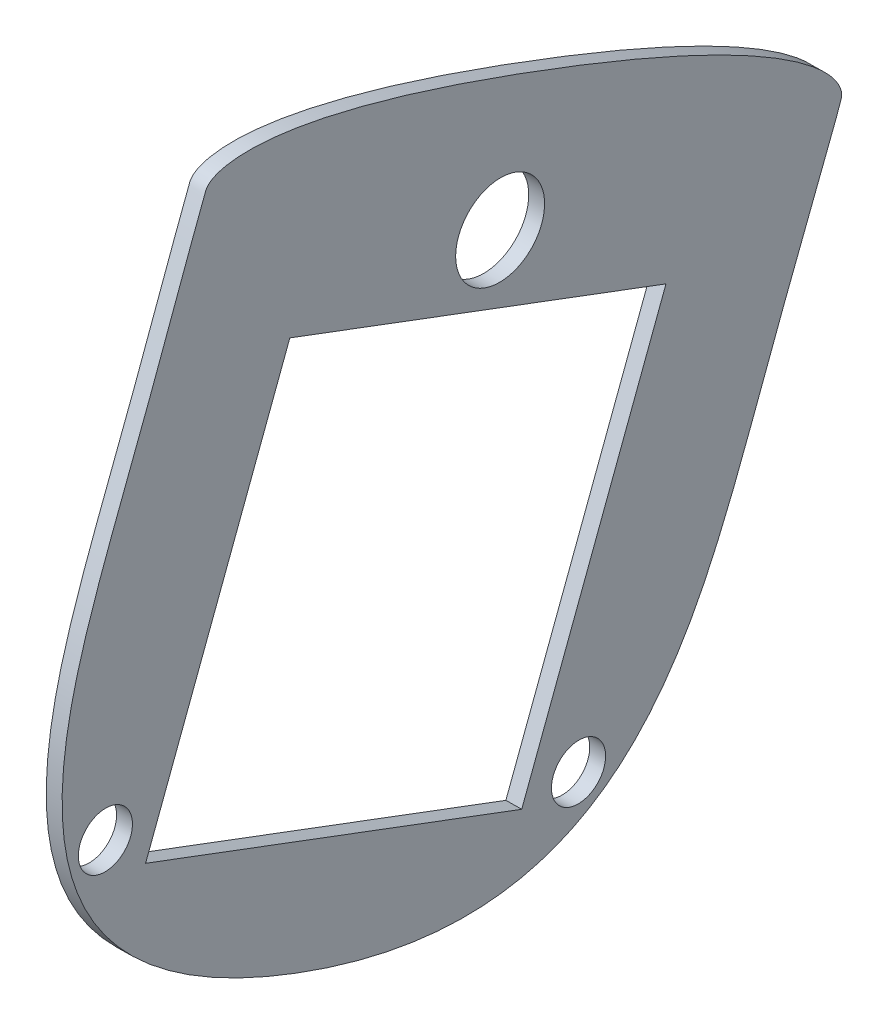
SolidWorks part; units mm, degrees
ref_plane "Front Plane" through (0, 0, 0) normal (0, 0, 1) x (1, 0, 0)
ref_plane "Top Plane" through (0, 0, 0) normal (0, 1, 0) x (1, 0, 0)
ref_plane "Right Plane" through (0, 0, 0) normal (1, 0, 0) x (0, 0, -1)
sketch "Sketch2" plane through (-865.3739, -0.0001, 10.9842) normal (-0.9999, 0, 0.0127) x (0.0127, 0, 0.9999)
  circle A0 centre (-17.1866, -9.2159) radius 6 construction
  circle A1 centre (105.1276, 37.6907) radius 6 construction
  circle A2 centre (-17.1866, -9.2159) radius 6
  circle A3 centre (105.1276, 37.6907) radius 6
  circle A4 centre (2.5155, 122.3361) radius 11.5 construction
  circle A5 centre (2.5155, 122.3361) radius 11.5
  point P0 (84.5639, 170.2439)
  point P1 (79.9592, 168.2953)
  dimension "D4" = 23
  dimension "D1" = 5
ref_plane "Plane1" through (-1179.5486, -0.0001, 14.972) normal (-0.9999, 0, 0.0127) x (0.0127, 0, 0.9999)
sketch "Sketch3" plane through (-1179.5486, -0.0001, 14.972) normal (-0.9999, 0, 0.0127) x (0.0127, 0, 0.9999)
  line L2 (-2.4987, -10.0092) -> (94.7364, 27.2797)
  line L6 (94.7364, 27.2797) -> (57.4475, 124.5149)
  line L7 (57.4475, 124.5149) -> (-39.7876, 87.2259)
  line L8 (-39.7876, 87.2259) -> (-2.4987, -10.0092)
  circle A3 centre (105.1276, 37.6907) radius 7
  circle A8 centre (3.0884, 120.8422) radius 11.5
  circle A9 centre (-17.1866, -9.2159) radius 7
  spline S0 degree 3 poles (84.5877, 169.5548) (84.1591, 170.6141) (83.6114, 171.6458) (82.4825, 172.9682) (81.1275, 174.0328) (79.6255, 174.8519) (78.0481, 175.4677) (75.8837, 176.0674) (73.1375, 176.4938) (69.8483, 176.6685) (66.5932, 176.6095) (63.379, 176.3823) (60.2073, 176.0282) (57.0754, 175.5759) (53.9806, 175.0444) (50.9193, 174.4483) (47.8886, 173.7975) (44.8855, 173.1008) (40.9147, 172.1178) (36.0066, 170.8019) (30.1862, 169.1128) (24.4167, 167.3312) (18.6809, 165.471) (12.9629, 163.5374) (7.2468, 161.5366) (-0.3928, 158.7797) (-6.166, 156.6131) (-13.9483, 153.6286) (-19.6897, 151.3795) (-27.2134, 148.3214) (-32.8014, 145.9872) (-38.3459, 143.6017) (-43.8547, 141.1498) (-49.3359, 138.6168) (-54.7932, 135.9811) (-59.3225, 133.6777) (-62.9324, 131.7536) (-65.6313, 130.2638) (-68.3201, 128.7213) (-70.995, 127.1176) (-73.6517, 125.4434) (-76.283, 123.6856) (-78.8782, 121.8282) (-81.4203, 119.8479) (-83.8804, 117.7153) (-86.2094, 115.386) (-87.9665, 113.2326) (-89.1751, 111.3395) (-89.9363, 109.8267) (-90.5056, 108.2133) (-90.8014, 106.5155) (-90.7567, 104.7772) (-90.474, 103.6437) (-90.0844, 102.5695) (-89.841, 101.912) (-89.5415, 101.1241) (-89.3902, 100.7305) (-89.238, 100.337) (-89.086, 99.9434) (-88.9335, 99.5497) (-88.7301, 99.0246) (-88.3735, 98.1053) (-87.8622, 96.7909) (-87.2459, 95.2119) (-86.6271, 93.6311) (-86.006, 92.0484) (-85.3828, 90.4637) (-84.7576, 88.8772) (-84.1306, 87.2885) (-83.5021, 85.6979) (-82.662, 83.5742) (-81.6087, 80.9142) (-80.341, 77.7134) (-79.0707, 74.5033) (-77.7994, 71.2836) (-76.5287, 68.0539) (-75.2594, 64.814) (-73.9927, 61.5637) (-72.7309, 58.3024) (-71.4763, 55.0294) (-69.81, 50.6514) (-67.733, 45.1559) (-65.1929, 38.5485) (-63.0021, 33.047) (-61.1797, 28.6615) (-60.0063, 25.9297) (-59.0438, 23.7513) (-58.3093, 22.1218) (-57.5611, 20.497) (-56.7986, 18.8776) (-56.0207, 17.2642) (-55.227, 15.6574) (-54.4159, 14.0579) (-52.7551, 10.8759) (-50.1136, 6.1705) (-46.2141, 0.1062) (-41.8798, -5.6826) (-37.071, -11.0955) (-31.7493, -16.031) (-26.8927, -19.6435) (-22.7717, -22.1827) (-18.509, -24.4734) (-12.9357, -26.8488) (-5.9687, -28.8976) (1.1735, -30.1678) (8.3946, -30.7243) (15.6292, -30.6392) (22.8222, -29.9927) (29.9449, -28.8562) (36.9714, -27.3105) (46.201, -24.7823) (52.9582, -22.4509) (61.8197, -19.0525) (68.4041, -16.2675) (76.9584, -11.9755) (83.2171, -8.426) (89.2737, -4.508) (95.0546, -0.1787) (100.4909, 4.596) (105.488, 9.8386) (109.9491, 15.5591) (113.7592, 21.7413) (116.3146, 27.2342) (117.9522, 31.7877) (119.3182, 36.4313) (120.5136, 42.3647) (121.1702, 49.5927) (121.1263, 56.8326) (120.4783, 64.0347) (119.3229, 71.151) (118.1408, 76.4157) (117.2481, 79.8921) (116.7817, 81.6236) (116.2975, 83.349) (115.7971, 85.0687) (115.2813, 86.7826) (114.7512, 88.4909) (114.2078, 90.1937) (113.467, 92.4568) (112.5129, 95.2725) (110.9356, 99.7518) (108.8862, 105.3072) (106.3571, 111.9184) (104.227, 117.3933) (102.5388, 121.7627) (101.2832, 125.0351) (100.0408, 128.3038) (98.8095, 131.5676) (97.5869, 134.8253) (96.3723, 138.0765) (95.1647, 141.3206) (93.9629, 144.5568) (92.7653, 147.7846) (91.7699, 150.4668) (90.9746, 152.6077) (90.3784, 154.2108) (89.7824, 155.8113) (89.1863, 157.4091) (88.5902, 159.0041) (87.9938, 160.5963) (87.3968, 162.1856) (86.7993, 163.7719) (86.3006, 165.0911) (85.9511, 166.0132) (85.7512, 166.5397) (85.6013, 166.9344) (85.4511, 167.3288) (85.3012, 167.7231) (85.1505, 168.117) (84.8464, 168.9032) (84.5877, 169.5548) (84.1591, 170.6141) (83.6114, 171.6458) knots -0.00321 -0.002568 0 0 0.002678 0.005356 0.008033 0.010711 0.013389 0.016067 0.021422 0.026778 0.032133 0.037489 0.042844 0.0482 0.053555 0.058911 0.064266 0.069622 0.074977 0.085688 0.096399 0.10711 0.117821 0.128532 0.139243 0.149955 0.171377 0.171377 0.192798 0.203509 0.21422 0.224931 0.235641 0.246352 0.257063 0.267774 0.273129 0.278485 0.28384 0.289196 0.294551 0.299906 0.305262 0.310617 0.315973 0.321328 0.326683 0.329361 0.332039 0.334717 0.337394 0.340072 0.34275 0.34275 0.345317 0.345958 0.3466 0.347242 0.347884 0.348525 0.349167 0.350451 0.353018 0.355585 0.358152 0.360719 0.363286 0.365853 0.36842 0.370987 0.373554 0.378688 0.383822 0.388956 0.39409 0.399224 0.404358 0.409492 0.414626 0.419761 0.424895 0.435163 0.445431 0.455699 0.460833 0.465967 0.468534 0.471101 0.473668 0.476235 0.478802 0.481369 0.483936 0.486503 0.496771 0.507039 0.517308 0.527576 0.537844 0.548112 0.553246 0.55838 0.568648 0.578916 0.589184 0.599453 0.609721 0.619989 0.630257 0.640525 0.650793 0.671329 0.671329 0.691871 0.702142 0.712413 0.722684 0.732955 0.743226 0.753497 0.763768 0.774039 0.78431 0.789445 0.794581 0.804852 0.815123 0.825394 0.835665 0.845936 0.856207 0.858774 0.861342 0.86391 0.866478 0.869045 0.871613 0.874181 0.876748 0.881884 0.887019 0.89729 0.907561 0.917832 0.922968 0.928103 0.933239 0.938374 0.94351 0.948645 0.953781 0.958916 0.964052 0.969187 0.971755 0.974323 0.97689 0.979458 0.982026 0.984594 0.987161 0.989729 0.992297 0.993581 0.994223 0.994865 0.995506 0.996148 0.99679 0.997432 1 1 1.002678 1.005356 1.008033 only from (84.3779, 170.0733) to (84.3779, 170.0733)
  spline S1 degree 3 poles (84.5877, 169.5548) (84.1591, 170.6141) (83.6114, 171.6458) (82.4825, 172.9682) (81.1275, 174.0328) (79.6255, 174.8519) (78.0481, 175.4677) (75.8837, 176.0674) (73.1375, 176.4938) (69.8483, 176.6685) (66.5932, 176.6095) (63.379, 176.3823) (60.2073, 176.0282) (57.0754, 175.5759) (53.9806, 175.0444) (50.9193, 174.4483) (47.8886, 173.7975) (44.8855, 173.1008) (40.9147, 172.1178) (36.0066, 170.8019) (30.1862, 169.1128) (24.4167, 167.3312) (18.6809, 165.471) (12.9629, 163.5374) (7.2468, 161.5366) (-0.3928, 158.7797) (-6.166, 156.6131) (-13.9483, 153.6286) (-19.6897, 151.3795) (-27.2134, 148.3214) (-32.8014, 145.9872) (-38.3459, 143.6017) (-43.8547, 141.1498) (-49.3359, 138.6168) (-54.7932, 135.9811) (-59.3225, 133.6777) (-62.9324, 131.7536) (-65.6313, 130.2638) (-68.3201, 128.7213) (-70.995, 127.1176) (-73.6517, 125.4434) (-76.283, 123.6856) (-78.8782, 121.8282) (-81.4203, 119.8479) (-83.8804, 117.7153) (-86.2094, 115.386) (-87.9665, 113.2326) (-89.1751, 111.3395) (-89.9363, 109.8267) (-90.5056, 108.2133) (-90.8014, 106.5155) (-90.7567, 104.7772) (-90.474, 103.6437) (-90.0844, 102.5695) (-89.841, 101.912) (-89.5415, 101.1241) (-89.3902, 100.7305) (-89.238, 100.337) (-89.086, 99.9434) (-88.9335, 99.5497) (-88.7301, 99.0246) (-88.3735, 98.1053) (-87.8622, 96.7909) (-87.2459, 95.2119) (-86.6271, 93.6311) (-86.006, 92.0484) (-85.3828, 90.4637) (-84.7576, 88.8772) (-84.1306, 87.2885) (-83.5021, 85.6979) (-82.662, 83.5742) (-81.6087, 80.9142) (-80.341, 77.7134) (-79.0707, 74.5033) (-77.7994, 71.2836) (-76.5287, 68.0539) (-75.2594, 64.814) (-73.9927, 61.5637) (-72.7309, 58.3024) (-71.4763, 55.0294) (-69.81, 50.6514) (-67.733, 45.1559) (-65.1929, 38.5485) (-63.0021, 33.047) (-61.1797, 28.6615) (-60.0063, 25.9297) (-59.0438, 23.7513) (-58.3093, 22.1218) (-57.5611, 20.497) (-56.7986, 18.8776) (-56.0207, 17.2642) (-55.227, 15.6574) (-54.4159, 14.0579) (-52.7551, 10.8759) (-50.1136, 6.1705) (-46.2141, 0.1062) (-41.8798, -5.6826) (-37.071, -11.0955) (-31.7493, -16.031) (-26.8927, -19.6435) (-22.7717, -22.1827) (-18.509, -24.4734) (-12.9357, -26.8488) (-5.9687, -28.8976) (1.1735, -30.1678) (8.3946, -30.7243) (15.6292, -30.6392) (22.8222, -29.9927) (29.9449, -28.8562) (36.9714, -27.3105) (46.201, -24.7823) (52.9582, -22.4509) (61.8197, -19.0525) (68.4041, -16.2675) (76.9584, -11.9755) (83.2171, -8.426) (89.2737, -4.508) (95.0546, -0.1787) (100.4909, 4.596) (105.488, 9.8386) (109.9491, 15.5591) (113.7592, 21.7413) (116.3146, 27.2342) (117.9522, 31.7877) (119.3182, 36.4313) (120.5136, 42.3647) (121.1702, 49.5927) (121.1263, 56.8326) (120.4783, 64.0347) (119.3229, 71.151) (118.1408, 76.4157) (117.2481, 79.8921) (116.7817, 81.6236) (116.2975, 83.349) (115.7971, 85.0687) (115.2813, 86.7826) (114.7512, 88.4909) (114.2078, 90.1937) (113.467, 92.4568) (112.5129, 95.2725) (110.9356, 99.7518) (108.8862, 105.3072) (106.3571, 111.9184) (104.227, 117.3933) (102.5388, 121.7627) (101.2832, 125.0351) (100.0408, 128.3038) (98.8095, 131.5676) (97.5869, 134.8253) (96.3723, 138.0765) (95.1647, 141.3206) (93.9629, 144.5568) (92.7653, 147.7846) (91.7699, 150.4668) (90.9746, 152.6077) (90.3784, 154.2108) (89.7824, 155.8113) (89.1863, 157.4091) (88.5902, 159.0041) (87.9938, 160.5963) (87.3968, 162.1856) (86.7993, 163.7719) (86.3006, 165.0911) (85.9511, 166.0132) (85.7512, 166.5397) (85.6013, 166.9344) (85.4511, 167.3288) (85.3012, 167.7231) (85.1505, 168.117) (84.8464, 168.9032) (84.5877, 169.5548) (84.1591, 170.6141) (83.6114, 171.6458) knots -0.00321 -0.002568 0 0 0.002678 0.005356 0.008033 0.010711 0.013389 0.016067 0.021422 0.026778 0.032133 0.037489 0.042844 0.0482 0.053555 0.058911 0.064266 0.069622 0.074977 0.085688 0.096399 0.10711 0.117821 0.128532 0.139243 0.149955 0.171377 0.171377 0.192798 0.203509 0.21422 0.224931 0.235641 0.246352 0.257063 0.267774 0.273129 0.278485 0.28384 0.289196 0.294551 0.299906 0.305262 0.310617 0.315973 0.321328 0.326683 0.329361 0.332039 0.334717 0.337394 0.340072 0.34275 0.34275 0.345317 0.345958 0.3466 0.347242 0.347884 0.348525 0.349167 0.350451 0.353018 0.355585 0.358152 0.360719 0.363286 0.365853 0.36842 0.370987 0.373554 0.378688 0.383822 0.388956 0.39409 0.399224 0.404358 0.409492 0.414626 0.419761 0.424895 0.435163 0.445431 0.455699 0.460833 0.465967 0.468534 0.471101 0.473668 0.476235 0.478802 0.481369 0.483936 0.486503 0.496771 0.507039 0.517308 0.527576 0.537844 0.548112 0.553246 0.55838 0.568648 0.578916 0.589184 0.599453 0.609721 0.619989 0.630257 0.640525 0.650793 0.671329 0.671329 0.691871 0.702142 0.712413 0.722684 0.732955 0.743226 0.753497 0.763768 0.774039 0.78431 0.789445 0.794581 0.804852 0.815123 0.825394 0.835665 0.845936 0.856207 0.858774 0.861342 0.86391 0.866478 0.869045 0.871613 0.874181 0.876748 0.881884 0.887019 0.89729 0.907561 0.917832 0.922968 0.928103 0.933239 0.938374 0.94351 0.948645 0.953781 0.958916 0.964052 0.969187 0.971755 0.974323 0.97689 0.979458 0.982026 0.984594 0.987161 0.989729 0.992297 0.993581 0.994223 0.994865 0.995506 0.996148 0.99679 0.997432 1 1 1.002678 1.005356 1.008033 only from (84.3779, 170.0733) to (84.3779, 170.0733)
  spline S2 degree 3 poles (79.7703, 168.0973) (79.654, 168.385) (79.5608, 168.567) (79.34, 168.909) (79.2107, 169.0695) (78.782, 169.5156) (78.4531, 169.7564) (77.7463, 170.1738) (77.3742, 170.347) (76.6181, 170.646) (76.2313, 170.7718) (75.4457, 170.9901) (75.0459, 171.0829) (74.2475, 171.2414) (73.8476, 171.3072) (72.6462, 171.473) (71.8432, 171.5429) (69.4298, 171.6691) (67.8151, 171.6433) (64.5792, 171.4656) (62.9671, 171.312) (59.7615, 170.9206) (58.1658, 170.6823) (54.9849, 170.1436) (53.3996, 169.8431) (48.656, 168.8688) (45.5068, 168.1227) (39.2498, 166.5091) (36.1403, 165.6406) (29.9484, 163.8155) (26.8662, 162.8586) (17.65, 159.8886) (11.5458, 157.7754) (-0.6049, 153.3792) (-6.6499, 151.0973) (-18.6886, 146.4029) (-24.6805, 143.9847) (-36.5791, 138.946) (-42.4872, 136.3273) (-51.2341, 132.1553) (-54.1301, 130.7232) (-59.8634, 127.7454) (-62.7011, 126.2002) (-66.8856, 123.7579) (-68.2675, 122.9231) (-70.9987, 121.2004) (-72.3487, 120.3119) (-74.9994, 118.4656) (-76.2997, 117.5087) (-78.8252, 115.4929) (-80.0492, 114.4377) (-81.7749, 112.7382) (-82.3328, 112.1498) (-83.3836, 110.9299) (-83.8771, 110.2969) (-84.5427, 109.2937) (-84.7517, 108.95) (-85.1321, 108.2356) (-85.3048, 107.8624) (-85.5131, 107.2891) (-85.5741, 107.0954) (-85.6734, 106.7005) (-85.7118, 106.4978) (-85.7567, 106.0923) (-85.7631, 105.8894) (-85.7375, 105.4833) (-85.7033, 105.2783) (-85.5978, 104.885) (-85.5239, 104.6959) (-85.3844, 104.3148) (-85.3142, 104.1244) (-85.1021, 103.5537) (-84.9587, 103.174) (-84.5227, 102.0368) (-84.2284, 101.28) (-83.3473, 99.0091) (-82.7572, 97.4963) (-77.4279, 83.8874) (-72.5683, 71.8388) (-66.7371, 56.6822) (-65.5847, 53.6454) (-63.2813, 47.5713) (-62.1268, 44.5353) (-59.771, 38.4819) (-58.5707, 35.464) (-56.7026, 30.9639) (-56.0686, 29.4684) (-54.7723, 26.4884) (-54.1097, 25.0035) (-50.7192, 17.6341) (-47.7589, 11.8968) (-42.5832, 3.7604) (-40.7366, 1.1258) (-37.7313, -2.6759) (-36.6901, -3.9179) (-35.0604, -5.7377) (-34.5059, -6.337) (-33.3724, -7.5201) (-32.7922, -8.1052) (-29.8441, -10.9713) (-27.345, -13.0666) (-23.3611, -15.8788) (-21.9939, -16.761) (-19.1769, -18.4096) (-17.7261, -19.1766) (-10.2663, -22.7) (-3.9825, -24.3776) (3.3729, -25.2321) (4.1924, -25.3124) (5.8269, -25.4445) (6.6433, -25.4963) (9.09, -25.6118) (10.7178, -25.6352) (15.5924, -25.5618) (18.8302, -25.3221) (23.6723, -24.7256) (25.2838, -24.487) (28.5025, -23.9384) (30.1115, -23.628) (34.9193, -22.6026) (38.0868, -21.7953) (44.3622, -19.9846) (47.4703, -18.982) (52.0947, -17.3537) (53.6299, -16.7903) (56.6886, -15.6251) (58.2124, -15.0236) (62.7493, -13.1641) (65.733, -11.8489) (71.6057, -9.0437) (74.4945, -7.5535) (80.1538, -4.3544) (82.9251, -2.6472) (86.9704, 0.1194) (88.3001, 1.0763) (90.263, 2.5701) (90.9119, 3.0777) (92.1913, 4.1078) (92.8227, 4.6309) (95.9368, 7.2882) (98.2906, 9.5479) (101.5765, 13.1758) (102.631, 14.4249) (104.1451, 16.3643) (104.6385, 17.0217) (105.6014, 18.3598) (106.0705, 19.0401) (108.3321, 22.4686) (109.8916, 25.3227) (112.4961, 31.2603) (113.5391, 34.3445) (114.5167, 38.3452) (114.696, 39.1533) (115.0193, 40.7681) (115.1639, 41.5767) (115.5483, 44.0063) (115.7388, 45.6309) (116.1311, 50.5177) (116.1533, 53.7931) (115.9328, 57.9055) (115.8763, 58.7278) (115.7406, 60.3643) (115.6615, 61.1797) (115.3922, 63.6178) (115.1705, 65.2327) (114.3953, 70.0494) (113.7318, 73.2236) (112.1864, 79.5171) (111.3038, 82.6361) (109.3954, 88.8382) (108.3675, 91.9207) (106.215, 98.0612) (105.0894, 101.1202) (102.7905, 107.2203) (101.6164, 110.261) (99.26, 116.3391) (98.0812, 119.3779) (95.7512, 125.4661) (94.5998, 128.5155) (91.1648, 137.6705) (88.9043, 143.7849) (85.4993, 152.9511) (84.362, 156.0057) (82.6444, 160.5831) (82.0699, 162.1082) (81.2041, 164.3942) (80.9151, 165.1561) (80.4796, 166.2982) (80.3329, 166.6783) (80.1095, 167.2472) (79.9971, 167.5314) (79.8836, 167.8152) (79.8078, 168.0043) (79.7703, 168.0973) (79.654, 168.385) (79.5608, 168.567) knots -0.000488 -0.000488 0 0 0.000977 0.000977 0.001953 0.001953 0.003906 0.003906 0.005859 0.005859 0.007812 0.007812 0.009766 0.009766 0.011719 0.011719 0.015625 0.015625 0.023437 0.023437 0.03125 0.03125 0.039062 0.039062 0.046875 0.046875 0.0625 0.0625 0.078125 0.078125 0.09375 0.09375 0.125 0.125 0.15625 0.15625 0.1875 0.1875 0.21875 0.21875 0.234375 0.234375 0.25 0.25 0.257812 0.257812 0.265625 0.265625 0.273437 0.273437 0.28125 0.28125 0.285156 0.285156 0.289062 0.289062 0.291016 0.291016 0.292969 0.292969 0.293945 0.293945 0.294922 0.294922 0.295898 0.295898 0.296875 0.296875 0.297852 0.297852 0.298828 0.298828 0.300781 0.300781 0.304687 0.304687 0.3125 0.3125 0.375 0.375 0.390625 0.390625 0.40625 0.40625 0.421875 0.421875 0.429687 0.429687 0.4375 0.4375 0.46875 0.46875 0.484375 0.484375 0.492187 0.492187 0.496094 0.496094 0.5 0.5 0.515625 0.515625 0.523437 0.523437 0.53125 0.53125 0.5625 0.5625 0.566406 0.566406 0.570312 0.570312 0.578125 0.578125 0.59375 0.59375 0.601562 0.601562 0.609375 0.609375 0.625 0.625 0.640625 0.640625 0.648437 0.648437 0.65625 0.65625 0.671875 0.671875 0.6875 0.6875 0.703125 0.703125 0.710937 0.710937 0.714844 0.714844 0.71875 0.71875 0.734375 0.734375 0.742187 0.742187 0.746094 0.746094 0.75 0.75 0.765625 0.765625 0.78125 0.78125 0.785156 0.785156 0.789062 0.789062 0.796875 0.796875 0.8125 0.8125 0.816406 0.816406 0.820312 0.820312 0.828125 0.828125 0.84375 0.84375 0.859375 0.859375 0.875 0.875 0.890625 0.890625 0.90625 0.90625 0.921875 0.921875 0.9375 0.9375 0.96875 0.96875 0.984375 0.984375 0.992187 0.992187 0.996094 0.996094 0.998047 0.998047 0.999023 0.999512 0.999512 1 1 1.000977 1.000977 1.001953 only from (79.7315, 168.1932) to (79.7315, 168.1932)
  spline S3 degree 3 poles (79.7703, 168.0973) (79.654, 168.385) (79.5608, 168.567) (79.34, 168.909) (79.2107, 169.0695) (78.782, 169.5156) (78.4531, 169.7564) (77.7463, 170.1738) (77.3742, 170.347) (76.6181, 170.646) (76.2313, 170.7718) (75.4457, 170.9901) (75.0459, 171.0829) (74.2475, 171.2414) (73.8476, 171.3072) (72.6462, 171.473) (71.8432, 171.5429) (69.4298, 171.6691) (67.8151, 171.6433) (64.5792, 171.4656) (62.9671, 171.312) (59.7615, 170.9206) (58.1658, 170.6823) (54.9849, 170.1436) (53.3996, 169.8431) (48.656, 168.8688) (45.5068, 168.1227) (39.2498, 166.5091) (36.1403, 165.6406) (29.9484, 163.8155) (26.8662, 162.8586) (17.65, 159.8886) (11.5458, 157.7754) (-0.6049, 153.3792) (-6.6499, 151.0973) (-18.6886, 146.4029) (-24.6805, 143.9847) (-36.5791, 138.946) (-42.4872, 136.3273) (-51.2341, 132.1553) (-54.1301, 130.7232) (-59.8634, 127.7454) (-62.7011, 126.2002) (-66.8856, 123.7579) (-68.2675, 122.9231) (-70.9987, 121.2004) (-72.3487, 120.3119) (-74.9994, 118.4656) (-76.2997, 117.5087) (-78.8252, 115.4929) (-80.0492, 114.4377) (-81.7749, 112.7382) (-82.3328, 112.1498) (-83.3836, 110.9299) (-83.8771, 110.2969) (-84.5427, 109.2937) (-84.7517, 108.95) (-85.1321, 108.2356) (-85.3048, 107.8624) (-85.5131, 107.2891) (-85.5741, 107.0954) (-85.6734, 106.7005) (-85.7118, 106.4978) (-85.7567, 106.0923) (-85.7631, 105.8894) (-85.7375, 105.4833) (-85.7033, 105.2783) (-85.5978, 104.885) (-85.5239, 104.6959) (-85.3844, 104.3148) (-85.3142, 104.1244) (-85.1021, 103.5537) (-84.9587, 103.174) (-84.5227, 102.0368) (-84.2284, 101.28) (-83.3473, 99.0091) (-82.7572, 97.4963) (-77.4279, 83.8874) (-72.5683, 71.8388) (-66.7371, 56.6822) (-65.5847, 53.6454) (-63.2813, 47.5713) (-62.1268, 44.5353) (-59.771, 38.4819) (-58.5707, 35.464) (-56.7026, 30.9639) (-56.0686, 29.4684) (-54.7723, 26.4884) (-54.1097, 25.0035) (-50.7192, 17.6341) (-47.7589, 11.8968) (-42.5832, 3.7604) (-40.7366, 1.1258) (-37.7313, -2.6759) (-36.6901, -3.9179) (-35.0604, -5.7377) (-34.5059, -6.337) (-33.3724, -7.5201) (-32.7922, -8.1052) (-29.8441, -10.9713) (-27.345, -13.0666) (-23.3611, -15.8788) (-21.9939, -16.761) (-19.1769, -18.4096) (-17.7261, -19.1766) (-10.2663, -22.7) (-3.9825, -24.3776) (3.3729, -25.2321) (4.1924, -25.3124) (5.8269, -25.4445) (6.6433, -25.4963) (9.09, -25.6118) (10.7178, -25.6352) (15.5924, -25.5618) (18.8302, -25.3221) (23.6723, -24.7256) (25.2838, -24.487) (28.5025, -23.9384) (30.1115, -23.628) (34.9193, -22.6026) (38.0868, -21.7953) (44.3622, -19.9846) (47.4703, -18.982) (52.0947, -17.3537) (53.6299, -16.7903) (56.6886, -15.6251) (58.2124, -15.0236) (62.7493, -13.1641) (65.733, -11.8489) (71.6057, -9.0437) (74.4945, -7.5535) (80.1538, -4.3544) (82.9251, -2.6472) (86.9704, 0.1194) (88.3001, 1.0763) (90.263, 2.5701) (90.9119, 3.0777) (92.1913, 4.1078) (92.8227, 4.6309) (95.9368, 7.2882) (98.2906, 9.5479) (101.5765, 13.1758) (102.631, 14.4249) (104.1451, 16.3643) (104.6385, 17.0217) (105.6014, 18.3598) (106.0705, 19.0401) (108.3321, 22.4686) (109.8916, 25.3227) (112.4961, 31.2603) (113.5391, 34.3445) (114.5167, 38.3452) (114.696, 39.1533) (115.0193, 40.7681) (115.1639, 41.5767) (115.5483, 44.0063) (115.7388, 45.6309) (116.1311, 50.5177) (116.1533, 53.7931) (115.9328, 57.9055) (115.8763, 58.7278) (115.7406, 60.3643) (115.6615, 61.1797) (115.3922, 63.6178) (115.1705, 65.2327) (114.3953, 70.0494) (113.7318, 73.2236) (112.1864, 79.5171) (111.3038, 82.6361) (109.3954, 88.8382) (108.3675, 91.9207) (106.215, 98.0612) (105.0894, 101.1202) (102.7905, 107.2203) (101.6164, 110.261) (99.26, 116.3391) (98.0812, 119.3779) (95.7512, 125.4661) (94.5998, 128.5155) (91.1648, 137.6705) (88.9043, 143.7849) (85.4993, 152.9511) (84.362, 156.0057) (82.6444, 160.5831) (82.0699, 162.1082) (81.2041, 164.3942) (80.9151, 165.1561) (80.4796, 166.2982) (80.3329, 166.6783) (80.1095, 167.2472) (79.9971, 167.5314) (79.8836, 167.8152) (79.8078, 168.0043) (79.7703, 168.0973) (79.654, 168.385) (79.5608, 168.567) knots -0.000488 -0.000488 0 0 0.000977 0.000977 0.001953 0.001953 0.003906 0.003906 0.005859 0.005859 0.007812 0.007812 0.009766 0.009766 0.011719 0.011719 0.015625 0.015625 0.023437 0.023437 0.03125 0.03125 0.039062 0.039062 0.046875 0.046875 0.0625 0.0625 0.078125 0.078125 0.09375 0.09375 0.125 0.125 0.15625 0.15625 0.1875 0.1875 0.21875 0.21875 0.234375 0.234375 0.25 0.25 0.257812 0.257812 0.265625 0.265625 0.273437 0.273437 0.28125 0.28125 0.285156 0.285156 0.289062 0.289062 0.291016 0.291016 0.292969 0.292969 0.293945 0.293945 0.294922 0.294922 0.295898 0.295898 0.296875 0.296875 0.297852 0.297852 0.298828 0.298828 0.300781 0.300781 0.304687 0.304687 0.3125 0.3125 0.375 0.375 0.390625 0.390625 0.40625 0.40625 0.421875 0.421875 0.429687 0.429687 0.4375 0.4375 0.46875 0.46875 0.484375 0.484375 0.492187 0.492187 0.496094 0.496094 0.5 0.5 0.515625 0.515625 0.523437 0.523437 0.53125 0.53125 0.5625 0.5625 0.566406 0.566406 0.570312 0.570312 0.578125 0.578125 0.59375 0.59375 0.601562 0.601562 0.609375 0.609375 0.625 0.625 0.640625 0.640625 0.648437 0.648437 0.65625 0.65625 0.671875 0.671875 0.6875 0.6875 0.703125 0.703125 0.710937 0.710937 0.714844 0.714844 0.71875 0.71875 0.734375 0.734375 0.742187 0.742187 0.746094 0.746094 0.75 0.75 0.765625 0.765625 0.78125 0.78125 0.785156 0.785156 0.789062 0.789062 0.796875 0.796875 0.8125 0.8125 0.816406 0.816406 0.820312 0.820312 0.828125 0.828125 0.84375 0.84375 0.859375 0.859375 0.875 0.875 0.890625 0.890625 0.90625 0.90625 0.921875 0.921875 0.9375 0.9375 0.96875 0.96875 0.984375 0.984375 0.992187 0.992187 0.996094 0.996094 0.998047 0.998047 0.999023 0.999512 0.999512 1 1 1.000977 1.000977 1.001953 only from (79.7315, 168.1932) to (79.7315, 168.1932)
extrude "Boss-Extrude1" add sketch "Sketch3" against normal blind 4 contours S1 S3 | S3 A8 A9 A3 region at (-1179.9823, -9.6438, -19.1964) region at (-1179.9212, -7.4934, -14.382)
sketch "Sketch7" plane through (-1175.549, -0.0001, 14.9212) normal (0.9999, 0, -0.0127) x (-0.0127, 0, -0.9999)
  spline S0 degree 3 poles (-55.9344, -16.6721) (-52.7593, -17.8897) (-49.662, -18.9903) (-43.4248, -21.0079) (-40.2853, -21.9261) (-33.9558, -23.5437) (-30.7657, -24.2432) (-24.3236, -25.3733) (-21.0713, -25.8034) (-16.9565, -26.127) (-16.1311, -26.181) (-14.4748, -26.2658) (-13.6441, -26.2966) (-11.1593, -26.3516) (-9.5077, -26.3387) (-4.5689, -26.1378) (-1.2977, -25.7881) (2.7595, -25.0278) (3.5693, -24.8594) (5.1855, -24.4882) (5.9938, -24.2848) (8.3992, -23.6239) (9.9716, -23.1179) (14.5951, -21.4043) (17.5519, -19.9997) (21.795, -17.4913) (23.1779, -16.5894) (25.2054, -15.1389) (25.8733, -14.6391) (27.1811, -13.6168) (27.8226, -13.0933) (30.9707, -10.4155) (33.3012, -8.0839) (36.5674, -4.3555) (37.6184, -3.0728) (39.647, -0.4409) (40.6168, 0.8978) (43.4116, 4.9725) (45.1232, 7.7665) (48.3192, 13.4707) (49.8019, 16.3817) (52.605, 22.2868) (53.9327, 25.277) (57.7665, 34.3242) (60.1255, 40.4588) (63.6065, 49.6767) (64.7573, 52.7529) (67.0792, 58.8976) (68.2524, 61.9653) (71.8055, 71.1558) (74.2132, 77.2674) (79.0359, 89.488) (81.4481, 95.5979) (83.9866, 102.0993) (84.136, 102.4817) (84.4258, 103.2499) (84.5675, 103.6354) (84.7755, 104.215) (84.8785, 104.5051) (84.9801, 104.7957) (85.0476, 104.9895) (85.0795, 105.087) (85.1584, 105.3849) (85.1922, 105.5918) (85.2188, 106.001) (85.2122, 106.2045) (85.1429, 106.812) (85.0347, 107.2151) (84.7563, 107.9822) (84.5839, 108.3519) (84.1965, 109.0731) (83.9816, 109.4238) (83.5298, 110.1006) (83.2914, 110.4284) (82.5477, 111.3874) (82.015, 111.9954) (80.9012, 113.1701) (80.3197, 113.7371) (78.5233, 115.3904) (77.2706, 116.4189) (74.7004, 118.3891) (73.3818, 119.3293) (70.6983, 121.1478) (69.3317, 122.0268) (65.1955, 124.5843) (62.3877, 126.1862) (56.7099, 129.2627) (53.8392, 130.736) (48.053, 133.5911) (45.1373, 134.9724) (36.3391, 139.0116) (30.4062, 141.5664) (18.4517, 146.495) (12.437, 148.8649) (0.3575, 153.4624) (-5.7095, 155.6873) (-17.9197, 159.9306) (-24.0658, 161.9525) (-33.3536, 164.7376) (-36.4615, 165.6241) (-42.7095, 167.2842) (-45.8516, 168.0588) (-50.5902, 169.0936) (-52.1739, 169.4175) (-55.3524, 170.0105) (-56.948, 170.2801) (-60.149, 170.7467) (-61.7537, 170.9438) (-64.975, 171.2342) (-66.5921, 171.3285) (-69.0162, 171.3467) (-69.8245, 171.3317) (-71.4416, 171.2454) (-72.2465, 171.1741) (-73.8395, 170.951) (-74.6285, 170.8003) (-75.7929, 170.4737) (-76.1779, 170.3485) (-76.938, 170.0459) (-77.3068, 169.8711) (-78.0045, 169.451) (-78.3381, 169.2042) (-78.7554, 168.7598) (-78.8827, 168.5968) (-79.0467, 168.3375) (-79.0968, 168.2491) (-79.1882, 168.0687) (-79.2286, 167.9762) (-79.58, 167.139) (-79.8837, 166.3911) (-80.3189, 165.2606) (-80.4603, 164.8822) (-80.745, 164.1263) (-80.8873, 163.7483) (-81.3137, 162.6142) (-81.5975, 161.8579) (-84.1493, 155.0506) (-86.4008, 148.9934) (-90.916, 136.8835) (-93.1837, 130.8324) (-96.6506, 121.7803) (-97.8207, 118.7684) (-100.1728, 112.7492) (-101.3532, 109.7412) (-103.6829, 103.7135) (-104.833, 100.6939) (-107.063, 94.6282) (-108.1436, 91.5799) (-111.2065, 82.3954) (-113.0223, 76.2184) (-114.9623, 66.7659) (-115.4811, 63.5845) (-116.0044, 58.7517) (-116.1362, 57.1261) (-116.2996, 53.8864) (-116.3318, 52.2699) (-116.2659, 47.4313) (-116.0068, 44.2201) (-115.3533, 40.2283) (-115.2061, 39.431) (-114.8776, 37.8388) (-114.6958, 37.0419) (-114.1019, 34.6725) (-113.6417, 33.1215) (-112.0666, 28.5554) (-110.7536, 25.6286) (-108.408, 21.4061) (-107.5634, 20.0266) (-106.2022, 17.9994) (-105.7327, 17.3308) (-104.7727, 16.0199) (-104.2811, 15.376) (-101.7683, 12.2102) (-99.5836, 9.8496) (-94.9256, 5.4129) (-92.4522, 3.3368) (-88.5627, 0.3997) (-87.2443, -0.5436) (-84.5745, -2.3625) (-83.222, -3.2388) (-79.1176, -5.7794) (-76.3195, -7.3564) (-70.6223, -10.3202) (-67.7233, -11.707) (-63.3121, -13.6689) (-61.831, -14.3028) (-59.5946, -15.2257) (-58.4727, -15.6801) (-57.1575, -16.1984) (-56.4984, -16.4547) (-56.2155, -16.5639) (-56.0269, -16.6365) (-55.9344, -16.6721) (-52.7593, -17.8897) (-49.662, -18.9903) knots -0.000488 -0.000488 0 0 0.015625 0.015625 0.03125 0.03125 0.046875 0.046875 0.0625 0.0625 0.066406 0.066406 0.070312 0.070312 0.078125 0.078125 0.09375 0.09375 0.097656 0.097656 0.101562 0.101562 0.109375 0.109375 0.125 0.125 0.132812 0.132812 0.136719 0.136719 0.140625 0.140625 0.15625 0.15625 0.164062 0.164062 0.171875 0.171875 0.1875 0.1875 0.203125 0.203125 0.21875 0.21875 0.25 0.25 0.265625 0.265625 0.28125 0.28125 0.3125 0.3125 0.34375 0.34375 0.345703 0.345703 0.347656 0.347656 0.348633 0.349121 0.349121 0.349609 0.349609 0.350586 0.350586 0.351562 0.351562 0.353516 0.353516 0.355469 0.355469 0.357422 0.357422 0.359375 0.359375 0.363281 0.363281 0.367187 0.367187 0.375 0.375 0.382812 0.382812 0.390625 0.390625 0.40625 0.40625 0.421875 0.421875 0.4375 0.4375 0.46875 0.46875 0.5 0.5 0.53125 0.53125 0.5625 0.5625 0.578125 0.578125 0.59375 0.59375 0.601562 0.601562 0.609375 0.609375 0.617187 0.617187 0.625 0.625 0.628906 0.628906 0.632812 0.632812 0.636719 0.636719 0.638672 0.638672 0.640625 0.640625 0.642578 0.642578 0.643555 0.643555 0.644043 0.644043 0.644531 0.644531 0.648437 0.648437 0.650391 0.650391 0.652344 0.652344 0.65625 0.65625 0.6875 0.6875 0.71875 0.71875 0.734375 0.734375 0.75 0.75 0.765625 0.765625 0.78125 0.78125 0.8125 0.8125 0.828125 0.828125 0.835937 0.835937 0.84375 0.84375 0.859375 0.859375 0.863281 0.863281 0.867187 0.867187 0.875 0.875 0.890625 0.890625 0.898437 0.898437 0.902344 0.902344 0.90625 0.90625 0.921875 0.921875 0.9375 0.9375 0.945312 0.945312 0.953125 0.953125 0.96875 0.96875 0.984375 0.984375 0.992187 0.992187 0.996094 0.998047 0.999023 0.999512 0.999512 1 1 1.015625 1.015625 1.03125 only from (-55.8382, -16.709) to (-55.8382, -16.709)
  spline S1 degree 3 poles (-55.9344, -16.6721) (-52.7593, -17.8897) (-49.662, -18.9903) (-43.4248, -21.0079) (-40.2853, -21.9261) (-33.9558, -23.5437) (-30.7657, -24.2432) (-24.3236, -25.3733) (-21.0713, -25.8034) (-16.9565, -26.127) (-16.1311, -26.181) (-14.4748, -26.2658) (-13.6441, -26.2966) (-11.1593, -26.3516) (-9.5077, -26.3387) (-4.5689, -26.1378) (-1.2977, -25.7881) (2.7595, -25.0278) (3.5693, -24.8594) (5.1855, -24.4882) (5.9938, -24.2848) (8.3992, -23.6239) (9.9716, -23.1179) (14.5951, -21.4043) (17.5519, -19.9997) (21.795, -17.4913) (23.1779, -16.5894) (25.2054, -15.1389) (25.8733, -14.6391) (27.1811, -13.6168) (27.8226, -13.0933) (30.9707, -10.4155) (33.3012, -8.0839) (36.5674, -4.3555) (37.6184, -3.0728) (39.647, -0.4409) (40.6168, 0.8978) (43.4116, 4.9725) (45.1232, 7.7665) (48.3192, 13.4707) (49.8019, 16.3817) (52.605, 22.2868) (53.9327, 25.277) (57.7665, 34.3242) (60.1255, 40.4588) (63.6065, 49.6767) (64.7573, 52.7529) (67.0792, 58.8976) (68.2524, 61.9653) (71.8055, 71.1558) (74.2132, 77.2674) (79.0359, 89.488) (81.4481, 95.5979) (83.9866, 102.0993) (84.136, 102.4817) (84.4258, 103.2499) (84.5675, 103.6354) (84.7755, 104.215) (84.8785, 104.5051) (84.9801, 104.7957) (85.0476, 104.9895) (85.0795, 105.087) (85.1584, 105.3849) (85.1922, 105.5918) (85.2188, 106.001) (85.2122, 106.2045) (85.1429, 106.812) (85.0347, 107.2151) (84.7563, 107.9822) (84.5839, 108.3519) (84.1965, 109.0731) (83.9816, 109.4238) (83.5298, 110.1006) (83.2914, 110.4284) (82.5477, 111.3874) (82.015, 111.9954) (80.9012, 113.1701) (80.3197, 113.7371) (78.5233, 115.3904) (77.2706, 116.4189) (74.7004, 118.3891) (73.3818, 119.3293) (70.6983, 121.1478) (69.3317, 122.0268) (65.1955, 124.5843) (62.3877, 126.1862) (56.7099, 129.2627) (53.8392, 130.736) (48.053, 133.5911) (45.1373, 134.9724) (36.3391, 139.0116) (30.4062, 141.5664) (18.4517, 146.495) (12.437, 148.8649) (0.3575, 153.4624) (-5.7095, 155.6873) (-17.9197, 159.9306) (-24.0658, 161.9525) (-33.3536, 164.7376) (-36.4615, 165.6241) (-42.7095, 167.2842) (-45.8516, 168.0588) (-50.5902, 169.0936) (-52.1739, 169.4175) (-55.3524, 170.0105) (-56.948, 170.2801) (-60.149, 170.7467) (-61.7537, 170.9438) (-64.975, 171.2342) (-66.5921, 171.3285) (-69.0162, 171.3467) (-69.8245, 171.3317) (-71.4416, 171.2454) (-72.2465, 171.1741) (-73.8395, 170.951) (-74.6285, 170.8003) (-75.7929, 170.4737) (-76.1779, 170.3485) (-76.938, 170.0459) (-77.3068, 169.8711) (-78.0045, 169.451) (-78.3381, 169.2042) (-78.7554, 168.7598) (-78.8827, 168.5968) (-79.0467, 168.3375) (-79.0968, 168.2491) (-79.1882, 168.0687) (-79.2286, 167.9762) (-79.58, 167.139) (-79.8837, 166.3911) (-80.3189, 165.2606) (-80.4603, 164.8822) (-80.745, 164.1263) (-80.8873, 163.7483) (-81.3137, 162.6142) (-81.5975, 161.8579) (-84.1493, 155.0506) (-86.4008, 148.9934) (-90.916, 136.8835) (-93.1837, 130.8324) (-96.6506, 121.7803) (-97.8207, 118.7684) (-100.1728, 112.7492) (-101.3532, 109.7412) (-103.6829, 103.7135) (-104.833, 100.6939) (-107.063, 94.6282) (-108.1436, 91.5799) (-111.2065, 82.3954) (-113.0223, 76.2184) (-114.9623, 66.7659) (-115.4811, 63.5845) (-116.0044, 58.7517) (-116.1362, 57.1261) (-116.2996, 53.8864) (-116.3318, 52.2699) (-116.2659, 47.4313) (-116.0068, 44.2201) (-115.3533, 40.2283) (-115.2061, 39.431) (-114.8776, 37.8388) (-114.6958, 37.0419) (-114.1019, 34.6725) (-113.6417, 33.1215) (-112.0666, 28.5554) (-110.7536, 25.6286) (-108.408, 21.4061) (-107.5634, 20.0266) (-106.2022, 17.9994) (-105.7327, 17.3308) (-104.7727, 16.0199) (-104.2811, 15.376) (-101.7683, 12.2102) (-99.5836, 9.8496) (-94.9256, 5.4129) (-92.4522, 3.3368) (-88.5627, 0.3997) (-87.2443, -0.5436) (-84.5745, -2.3625) (-83.222, -3.2388) (-79.1176, -5.7794) (-76.3195, -7.3564) (-70.6223, -10.3202) (-67.7233, -11.707) (-63.3121, -13.6689) (-61.831, -14.3028) (-59.5946, -15.2257) (-58.4727, -15.6801) (-57.1575, -16.1984) (-56.4984, -16.4547) (-56.2155, -16.5639) (-56.0269, -16.6365) (-55.9344, -16.6721) (-52.7593, -17.8897) (-49.662, -18.9903) knots -0.000488 -0.000488 0 0 0.015625 0.015625 0.03125 0.03125 0.046875 0.046875 0.0625 0.0625 0.066406 0.066406 0.070312 0.070312 0.078125 0.078125 0.09375 0.09375 0.097656 0.097656 0.101562 0.101562 0.109375 0.109375 0.125 0.125 0.132812 0.132812 0.136719 0.136719 0.140625 0.140625 0.15625 0.15625 0.164062 0.164062 0.171875 0.171875 0.1875 0.1875 0.203125 0.203125 0.21875 0.21875 0.25 0.25 0.265625 0.265625 0.28125 0.28125 0.3125 0.3125 0.34375 0.34375 0.345703 0.345703 0.347656 0.347656 0.348633 0.349121 0.349121 0.349609 0.349609 0.350586 0.350586 0.351562 0.351562 0.353516 0.353516 0.355469 0.355469 0.357422 0.357422 0.359375 0.359375 0.363281 0.363281 0.367187 0.367187 0.375 0.375 0.382812 0.382812 0.390625 0.390625 0.40625 0.40625 0.421875 0.421875 0.4375 0.4375 0.46875 0.46875 0.5 0.5 0.53125 0.53125 0.5625 0.5625 0.578125 0.578125 0.59375 0.59375 0.601562 0.601562 0.609375 0.609375 0.617187 0.617187 0.625 0.625 0.628906 0.628906 0.632812 0.632812 0.636719 0.636719 0.638672 0.638672 0.640625 0.640625 0.642578 0.642578 0.643555 0.643555 0.644043 0.644043 0.644531 0.644531 0.648437 0.648437 0.650391 0.650391 0.652344 0.652344 0.65625 0.65625 0.6875 0.6875 0.71875 0.71875 0.734375 0.734375 0.75 0.75 0.765625 0.765625 0.78125 0.78125 0.8125 0.8125 0.828125 0.828125 0.835937 0.835937 0.84375 0.84375 0.859375 0.859375 0.863281 0.863281 0.867187 0.867187 0.875 0.875 0.890625 0.890625 0.898437 0.898437 0.902344 0.902344 0.90625 0.90625 0.921875 0.921875 0.9375 0.9375 0.945312 0.945312 0.953125 0.953125 0.96875 0.96875 0.984375 0.984375 0.992187 0.992187 0.996094 0.998047 0.999023 0.999512 0.999512 1 1 1.015625 1.015625 1.03125 only from (-55.8382, -16.709) to (-55.8382, -16.709)
  spline S2 degree 3 poles (-84.1591, 170.6141) (-84.5877, 169.5548) (-84.8464, 168.9032) (-85.1505, 168.117) (-85.3012, 167.7231) (-85.4511, 167.3288) (-85.6013, 166.9344) (-85.7512, 166.5397) (-85.9511, 166.0132) (-86.3006, 165.0911) (-86.7993, 163.7719) (-87.3968, 162.1856) (-87.9938, 160.5963) (-88.5902, 159.0041) (-89.1863, 157.4091) (-89.7824, 155.8113) (-90.3784, 154.2108) (-90.9746, 152.6077) (-91.7699, 150.4668) (-92.7653, 147.7846) (-93.9629, 144.5568) (-95.1647, 141.3206) (-96.3723, 138.0765) (-97.5869, 134.8253) (-98.8095, 131.5676) (-100.0408, 128.3038) (-101.2832, 125.0351) (-102.5388, 121.7627) (-104.227, 117.3933) (-106.3571, 111.9184) (-108.8862, 105.3072) (-110.9356, 99.7518) (-112.5129, 95.2725) (-113.467, 92.4568) (-114.2078, 90.1937) (-114.7512, 88.4909) (-115.2813, 86.7826) (-115.7971, 85.0687) (-116.2975, 83.349) (-116.7817, 81.6236) (-117.2481, 79.8921) (-118.1408, 76.4157) (-119.3229, 71.151) (-120.4783, 64.0347) (-121.1263, 56.8326) (-121.1702, 49.5927) (-120.5136, 42.3647) (-119.3182, 36.4313) (-117.9522, 31.7877) (-116.3146, 27.2342) (-113.7592, 21.7413) (-109.9491, 15.5591) (-105.488, 9.8386) (-100.4909, 4.596) (-95.0546, -0.1787) (-89.2737, -4.508) (-83.2171, -8.426) (-76.9584, -11.9755) (-68.4041, -16.2675) (-61.8197, -19.0525) (-52.9582, -22.4509) (-46.201, -24.7823) (-36.9714, -27.3105) (-29.9449, -28.8562) (-22.8222, -29.9927) (-15.6292, -30.6392) (-8.3946, -30.7243) (-1.1735, -30.1678) (5.9687, -28.8976) (12.9357, -26.8488) (18.509, -24.4734) (22.7717, -22.1827) (26.8927, -19.6435) (31.7493, -16.031) (37.071, -11.0955) (41.8798, -5.6826) (46.2141, 0.1062) (50.1136, 6.1705) (52.7551, 10.8759) (54.4159, 14.0579) (55.227, 15.6574) (56.0207, 17.2642) (56.7986, 18.8776) (57.5611, 20.497) (58.3093, 22.1218) (59.0438, 23.7513) (60.0063, 25.9297) (61.1797, 28.6615) (63.0021, 33.047) (65.1929, 38.5485) (67.733, 45.1559) (69.81, 50.6514) (71.4763, 55.0294) (72.7309, 58.3024) (73.9927, 61.5637) (75.2594, 64.814) (76.5287, 68.0539) (77.7994, 71.2836) (79.0707, 74.5033) (80.341, 77.7134) (81.6087, 80.9142) (82.662, 83.5742) (83.5021, 85.6979) (84.1306, 87.2885) (84.7576, 88.8772) (85.3828, 90.4637) (86.006, 92.0484) (86.6271, 93.6311) (87.2459, 95.2119) (87.8622, 96.7909) (88.3735, 98.1053) (88.7301, 99.0246) (88.9335, 99.5497) (89.086, 99.9434) (89.238, 100.337) (89.3902, 100.7305) (89.5415, 101.1241) (89.841, 101.912) (90.0844, 102.5695) (90.474, 103.6437) (90.7567, 104.7772) (90.8014, 106.5155) (90.5056, 108.2133) (89.9363, 109.8267) (89.1751, 111.3395) (87.9665, 113.2326) (86.2094, 115.386) (83.8804, 117.7153) (81.4203, 119.8479) (78.8782, 121.8282) (76.283, 123.6856) (73.6517, 125.4434) (70.995, 127.1176) (68.3201, 128.7213) (65.6313, 130.2638) (62.9324, 131.7536) (59.3225, 133.6777) (54.7932, 135.9811) (49.3359, 138.6168) (43.8547, 141.1498) (38.3459, 143.6017) (32.8014, 145.9872) (27.2134, 148.3214) (19.6897, 151.3795) (13.9483, 153.6286) (6.166, 156.6131) (0.3928, 158.7797) (-7.2468, 161.5366) (-12.9629, 163.5374) (-18.6809, 165.471) (-24.4167, 167.3312) (-30.1862, 169.1128) (-36.0066, 170.8019) (-40.9147, 172.1178) (-44.8855, 173.1008) (-47.8886, 173.7975) (-50.9193, 174.4483) (-53.9806, 175.0444) (-57.0754, 175.5759) (-60.2073, 176.0282) (-63.379, 176.3823) (-66.5932, 176.6095) (-69.8483, 176.6685) (-73.1375, 176.4938) (-75.8837, 176.0674) (-78.0481, 175.4677) (-79.6255, 174.8519) (-81.1275, 174.0328) (-82.4825, 172.9682) (-83.6114, 171.6458) (-84.1591, 170.6141) (-84.5877, 169.5548) (-84.8464, 168.9032) knots -0.005356 -0.002678 0 0 0.002568 0.00321 0.003852 0.004494 0.005135 0.005777 0.006419 0.007703 0.010271 0.012839 0.015406 0.017974 0.020542 0.02311 0.025677 0.028245 0.030813 0.035948 0.041084 0.046219 0.051355 0.05649 0.061626 0.066761 0.071897 0.077032 0.082168 0.092439 0.10271 0.112981 0.118116 0.123252 0.125819 0.128387 0.130955 0.133522 0.13609 0.138658 0.141226 0.143793 0.154064 0.164335 0.174606 0.184877 0.195148 0.205419 0.210555 0.21569 0.225961 0.236232 0.246503 0.256774 0.267045 0.277316 0.287587 0.297858 0.308129 0.328671 0.328671 0.349207 0.359475 0.369743 0.380011 0.390279 0.400547 0.410816 0.421084 0.431352 0.44162 0.446754 0.451888 0.462156 0.472424 0.482692 0.492961 0.503229 0.513497 0.516064 0.518631 0.521198 0.523765 0.526332 0.528899 0.531466 0.534033 0.539167 0.544301 0.554569 0.564837 0.575105 0.580239 0.585374 0.590508 0.595642 0.600776 0.60591 0.611044 0.616178 0.621312 0.626446 0.629013 0.63158 0.634147 0.636714 0.639281 0.641848 0.644415 0.646982 0.649549 0.650833 0.651475 0.652116 0.652758 0.6534 0.654042 0.654683 0.65725 0.65725 0.659928 0.662606 0.665283 0.667961 0.670639 0.673317 0.678672 0.684027 0.689383 0.694738 0.700094 0.705449 0.710804 0.71616 0.721515 0.726871 0.732226 0.742937 0.753648 0.764359 0.775069 0.78578 0.796491 0.807202 0.828623 0.828623 0.850045 0.860757 0.871468 0.882179 0.89289 0.903601 0.914312 0.925023 0.930378 0.935734 0.941089 0.946445 0.9518 0.957156 0.962511 0.967867 0.973222 0.978578 0.983933 0.986611 0.989289 0.991967 0.994644 0.997322 1 1 1.002568 1.00321 1.003852 only from (-84.3779, 170.0733) to (-84.3779, 170.0733) construction
  spline S3 degree 3 poles (-84.1591, 170.6141) (-84.5877, 169.5548) (-84.8464, 168.9032) (-85.1505, 168.117) (-85.3012, 167.7231) (-85.4511, 167.3288) (-85.6013, 166.9344) (-85.7512, 166.5397) (-85.9511, 166.0132) (-86.3006, 165.0911) (-86.7993, 163.7719) (-87.3968, 162.1856) (-87.9938, 160.5963) (-88.5902, 159.0041) (-89.1863, 157.4091) (-89.7824, 155.8113) (-90.3784, 154.2108) (-90.9746, 152.6077) (-91.7699, 150.4668) (-92.7653, 147.7846) (-93.9629, 144.5568) (-95.1647, 141.3206) (-96.3723, 138.0765) (-97.5869, 134.8253) (-98.8095, 131.5676) (-100.0408, 128.3038) (-101.2832, 125.0351) (-102.5388, 121.7627) (-104.227, 117.3933) (-106.3571, 111.9184) (-108.8862, 105.3072) (-110.9356, 99.7518) (-112.5129, 95.2725) (-113.467, 92.4568) (-114.2078, 90.1937) (-114.7512, 88.4909) (-115.2813, 86.7826) (-115.7971, 85.0687) (-116.2975, 83.349) (-116.7817, 81.6236) (-117.2481, 79.8921) (-118.1408, 76.4157) (-119.3229, 71.151) (-120.4783, 64.0347) (-121.1263, 56.8326) (-121.1702, 49.5927) (-120.5136, 42.3647) (-119.3182, 36.4313) (-117.9522, 31.7877) (-116.3146, 27.2342) (-113.7592, 21.7413) (-109.9491, 15.5591) (-105.488, 9.8386) (-100.4909, 4.596) (-95.0546, -0.1787) (-89.2737, -4.508) (-83.2171, -8.426) (-76.9584, -11.9755) (-68.4041, -16.2675) (-61.8197, -19.0525) (-52.9582, -22.4509) (-46.201, -24.7823) (-36.9714, -27.3105) (-29.9449, -28.8562) (-22.8222, -29.9927) (-15.6292, -30.6392) (-8.3946, -30.7243) (-1.1735, -30.1678) (5.9687, -28.8976) (12.9357, -26.8488) (18.509, -24.4734) (22.7717, -22.1827) (26.8927, -19.6435) (31.7493, -16.031) (37.071, -11.0955) (41.8798, -5.6826) (46.2141, 0.1062) (50.1136, 6.1705) (52.7551, 10.8759) (54.4159, 14.0579) (55.227, 15.6574) (56.0207, 17.2642) (56.7986, 18.8776) (57.5611, 20.497) (58.3093, 22.1218) (59.0438, 23.7513) (60.0063, 25.9297) (61.1797, 28.6615) (63.0021, 33.047) (65.1929, 38.5485) (67.733, 45.1559) (69.81, 50.6514) (71.4763, 55.0294) (72.7309, 58.3024) (73.9927, 61.5637) (75.2594, 64.814) (76.5287, 68.0539) (77.7994, 71.2836) (79.0707, 74.5033) (80.341, 77.7134) (81.6087, 80.9142) (82.662, 83.5742) (83.5021, 85.6979) (84.1306, 87.2885) (84.7576, 88.8772) (85.3828, 90.4637) (86.006, 92.0484) (86.6271, 93.6311) (87.2459, 95.2119) (87.8622, 96.7909) (88.3735, 98.1053) (88.7301, 99.0246) (88.9335, 99.5497) (89.086, 99.9434) (89.238, 100.337) (89.3902, 100.7305) (89.5415, 101.1241) (89.841, 101.912) (90.0844, 102.5695) (90.474, 103.6437) (90.7567, 104.7772) (90.8014, 106.5155) (90.5056, 108.2133) (89.9363, 109.8267) (89.1751, 111.3395) (87.9665, 113.2326) (86.2094, 115.386) (83.8804, 117.7153) (81.4203, 119.8479) (78.8782, 121.8282) (76.283, 123.6856) (73.6517, 125.4434) (70.995, 127.1176) (68.3201, 128.7213) (65.6313, 130.2638) (62.9324, 131.7536) (59.3225, 133.6777) (54.7932, 135.9811) (49.3359, 138.6168) (43.8547, 141.1498) (38.3459, 143.6017) (32.8014, 145.9872) (27.2134, 148.3214) (19.6897, 151.3795) (13.9483, 153.6286) (6.166, 156.6131) (0.3928, 158.7797) (-7.2468, 161.5366) (-12.9629, 163.5374) (-18.6809, 165.471) (-24.4167, 167.3312) (-30.1862, 169.1128) (-36.0066, 170.8019) (-40.9147, 172.1178) (-44.8855, 173.1008) (-47.8886, 173.7975) (-50.9193, 174.4483) (-53.9806, 175.0444) (-57.0754, 175.5759) (-60.2073, 176.0282) (-63.379, 176.3823) (-66.5932, 176.6095) (-69.8483, 176.6685) (-73.1375, 176.4938) (-75.8837, 176.0674) (-78.0481, 175.4677) (-79.6255, 174.8519) (-81.1275, 174.0328) (-82.4825, 172.9682) (-83.6114, 171.6458) (-84.1591, 170.6141) (-84.5877, 169.5548) (-84.8464, 168.9032) knots -0.005356 -0.002678 0 0 0.002568 0.00321 0.003852 0.004494 0.005135 0.005777 0.006419 0.007703 0.010271 0.012839 0.015406 0.017974 0.020542 0.02311 0.025677 0.028245 0.030813 0.035948 0.041084 0.046219 0.051355 0.05649 0.061626 0.066761 0.071897 0.077032 0.082168 0.092439 0.10271 0.112981 0.118116 0.123252 0.125819 0.128387 0.130955 0.133522 0.13609 0.138658 0.141226 0.143793 0.154064 0.164335 0.174606 0.184877 0.195148 0.205419 0.210555 0.21569 0.225961 0.236232 0.246503 0.256774 0.267045 0.277316 0.287587 0.297858 0.308129 0.328671 0.328671 0.349207 0.359475 0.369743 0.380011 0.390279 0.400547 0.410816 0.421084 0.431352 0.44162 0.446754 0.451888 0.462156 0.472424 0.482692 0.492961 0.503229 0.513497 0.516064 0.518631 0.521198 0.523765 0.526332 0.528899 0.531466 0.534033 0.539167 0.544301 0.554569 0.564837 0.575105 0.580239 0.585374 0.590508 0.595642 0.600776 0.60591 0.611044 0.616178 0.621312 0.626446 0.629013 0.63158 0.634147 0.636714 0.639281 0.641848 0.644415 0.646982 0.649549 0.650833 0.651475 0.652116 0.652758 0.6534 0.654042 0.654683 0.65725 0.65725 0.659928 0.662606 0.665283 0.667961 0.670639 0.673317 0.678672 0.684027 0.689383 0.694738 0.700094 0.705449 0.710804 0.71616 0.721515 0.726871 0.732226 0.742937 0.753648 0.764359 0.775069 0.78578 0.796491 0.807202 0.828623 0.828623 0.850045 0.860757 0.871468 0.882179 0.89289 0.903601 0.914312 0.925023 0.930378 0.935734 0.941089 0.946445 0.9518 0.957156 0.962511 0.967867 0.973222 0.978578 0.983933 0.986611 0.989289 0.991967 0.994644 0.997322 1 1 1.002568 1.00321 1.003852 only from (-84.3779, 170.0733) to (-84.3779, 170.0733)
extrude "Cut-Extrude1" cut sketch "Sketch7" against normal through all both and the other way through all
